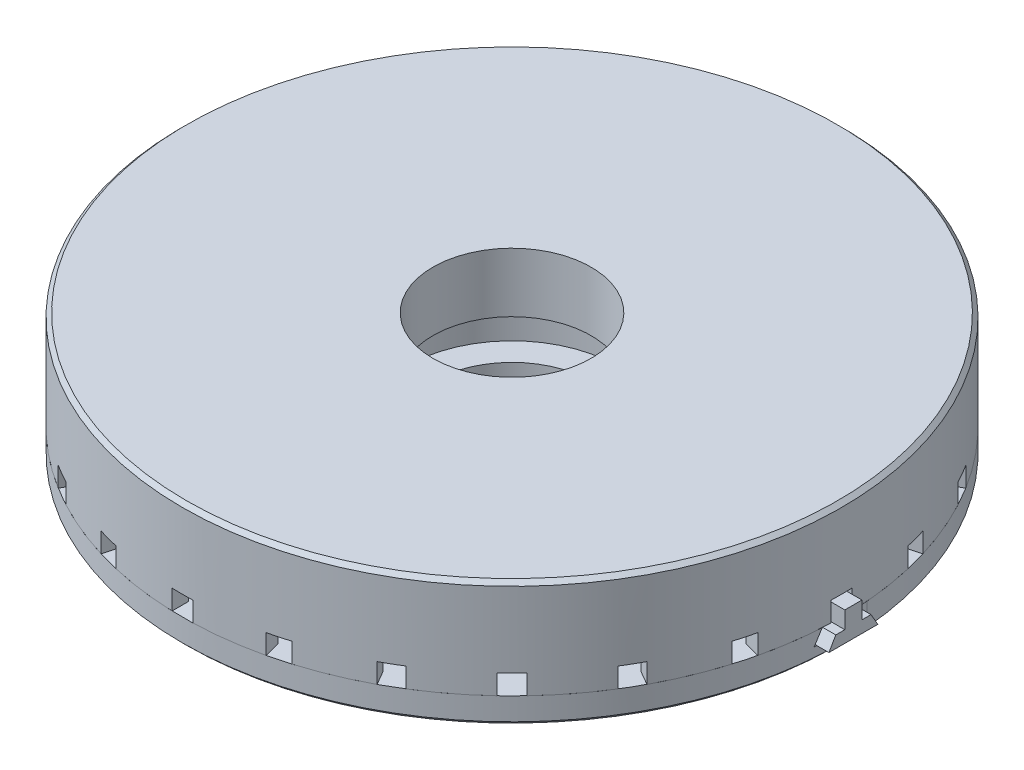
SolidWorks part; units mm, degrees
other "Base_fija"
other "Seguro"
other "Plato_gira"
ref_plane "Front Plane" through (0, 0, 0) normal (0, 0, 1) x (1, 0, 0)
ref_plane "Top Plane" through (0, 0, 0) normal (0, 1, 0) x (1, 0, 0)
ref_plane "Right Plane" through (0, 0, 0) normal (1, 0, 0) x (0, 0, -1)
ref_plane "Plano_Top Plane_+16" through (0, 16, 0) normal (0, 1, 0) x (1, 0, 0)
sketch "Croquis_plato" plane through (0, 16, 0) normal (0, 1, 0) x (1, 0, 0)
  circle A0 centre (0, 0) radius 50
  dimension "D1" = 100
extrude "Plato" add sketch "Croquis_plato" along normal blind 3
sketch "Croquis_falda" plane through (0, 16, 0) normal (0, 1, 0) x (1, 0, 0)
  circle A0 centre (0, 0) radius 50
  circle A1 centre (0, 0) radius 47.5
  dimension "D1" = 95
extrude "Falda" add sketch "Croquis_falda" against normal blind 12
sketch "Croquis_dedos" plane through (0, 0, 0) normal (0, 0, 1) x (1, 0, 0)
  line L0 (0, 0) -> (0, 20) construction
  line L1 (23.3, 16.5) -> (24.5, 16.5)
  line L2 (24.5, 16.5) -> (24.5, 4.5)
  line L3 (24.5, 4.5) -> (23, 4.5)
  line L4 (23, 4.5) -> (22.3, 5.2)
  line L5 (22.3, 5.2) -> (22.3, 5.5)
  line L6 (22.3, 5.5) -> (23.3, 6.5)
  line L7 (23.3, 6.5) -> (23.3, 16.5)
revolve "Anillo_dedos" add sketch "Croquis_dedos" angle 360 about L0
sketch "Croquis_espiga" plane through (0, 16, 0) normal (0, 1, 0) x (1, 0, 0)
  circle A0 centre (0, 0) radius 15.75
  circle A1 centre (0, 0) radius 12
  dimension "D1" = 31.5
extrude "Espiga_centrado" add sketch "Croquis_espiga" against normal blind 6
sketch "Croquis_paso_cables" plane through (0, 0, 0) normal (0, 1, 0) x (1, 0, 0)
  circle A0 centre (0, 0) radius 12
  dimension "D1" = 24
extrude "Paso_cables" cut sketch "Croquis_paso_cables" along normal through all and the other way through all
ref_plane "Plano_Top Plane_+4" through (0, 4, 0) normal (0, 1, 0) x (1, 0, 0)
sketch "Croquis_separar_dedos" plane through (0, 4, 0) normal (0, 1, 0) x (1, 0, 0)
  line L0 (21.4214, 4.5533) -> (24.4537, 5.1978)
  line L1 (18.3669, 11.9276) -> (20.9668, 13.616)
  line L2 (11.9276, 18.3669) -> (13.616, 20.9668)
  line L3 (4.5533, 21.4214) -> (5.1978, 24.4537)
  line L4 (-4.5533, 21.4214) -> (-5.1978, 24.4537)
  line L5 (-11.9276, 18.3669) -> (-13.616, 20.9668)
  line L6 (-18.3669, 11.9276) -> (-20.9668, 13.616)
  line L7 (-21.4214, 4.5533) -> (-24.4537, 5.1978)
  line L8 (-21.4214, -4.5533) -> (-24.4537, -5.1978)
  line L9 (-18.3669, -11.9276) -> (-20.9668, -13.616)
  line L10 (-11.9276, -18.3669) -> (-13.616, -20.9668)
  line L11 (-4.5533, -21.4214) -> (-5.1978, -24.4537)
  line L12 (4.5533, -21.4214) -> (5.1978, -24.4537)
  line L13 (11.9276, -18.3669) -> (13.616, -20.9668)
  line L14 (18.3669, -11.9276) -> (20.9668, -13.616)
  line L15 (21.4214, -4.5533) -> (24.4537, -5.1978)
  arc A0 (24.4537, 5.1978) -> (20.9668, 13.616) centre (0, 0) ccw
  arc A1 (21.4214, 4.5533) -> (18.3669, 11.9276) centre (0, 0) ccw
  arc A2 (13.616, 20.9668) -> (5.1978, 24.4537) centre (0, 0) ccw
  arc A3 (11.9276, 18.3669) -> (4.5533, 21.4214) centre (0, 0) ccw
  arc A4 (-5.1978, 24.4537) -> (-13.616, 20.9668) centre (0, 0) ccw
  arc A5 (-4.5533, 21.4214) -> (-11.9276, 18.3669) centre (0, 0) ccw
  arc A6 (-20.9668, 13.616) -> (-24.4537, 5.1978) centre (0, 0) ccw
  arc A7 (-18.3669, 11.9276) -> (-21.4214, 4.5533) centre (0, 0) ccw
  arc A8 (-24.4537, -5.1978) -> (-20.9668, -13.616) centre (0, 0) ccw
  arc A9 (-21.4214, -4.5533) -> (-18.3669, -11.9276) centre (0, 0) ccw
  arc A10 (-13.616, -20.9668) -> (-5.1978, -24.4537) centre (0, 0) ccw
  arc A11 (-11.9276, -18.3669) -> (-4.5533, -21.4214) centre (0, 0) ccw
  arc A12 (5.1978, -24.4537) -> (13.616, -20.9668) centre (0, 0) ccw
  arc A13 (4.5533, -21.4214) -> (11.9276, -18.3669) centre (0, 0) ccw
  arc A14 (20.9668, -13.616) -> (24.4537, -5.1978) centre (0, 0) ccw
  arc A15 (18.3669, -11.9276) -> (21.4214, -4.5533) centre (0, 0) ccw
extrude "Separar_dedos" cut sketch "Croquis_separar_dedos" along normal blind 12
sketch "Croquis_muescas" plane through (0, 4, 0) normal (0, 1, 0) x (1, 0, 0)
  line L0 (46.5, -1.6) -> (51, -1.6)
  line L1 (51, -1.6) -> (51, 1.6)
  line L2 (51, 1.6) -> (46.5, 1.6)
  line L3 (46.5, 1.6) -> (46.5, -1.6)
  line L4 (45.3297, 10.4896) -> (49.6763, 11.6543)
  line L5 (49.6763, 11.6543) -> (48.8481, 14.7453)
  line L6 (48.8481, 14.7453) -> (44.5014, 13.5806)
  line L7 (44.5014, 13.5806) -> (45.3297, 10.4896)
  line L8 (41.0702, 21.8644) -> (44.9673, 24.1144)
  line L9 (44.9673, 24.1144) -> (43.3673, 26.8856)
  line L10 (43.3673, 26.8856) -> (39.4702, 24.6356)
  line L11 (39.4702, 24.6356) -> (41.0702, 21.8644)
  line L12 (34.0118, 31.7491) -> (37.1938, 34.9311)
  line L13 (37.1938, 34.9311) -> (34.9311, 37.1938)
  line L14 (34.9311, 37.1938) -> (31.7491, 34.0118)
  line L15 (31.7491, 34.0118) -> (34.0118, 31.7491)
  line L16 (24.6356, 39.4702) -> (26.8856, 43.3673)
  line L17 (26.8856, 43.3673) -> (24.1144, 44.9673)
  line L18 (24.1144, 44.9673) -> (21.8644, 41.0702)
  line L19 (21.8644, 41.0702) -> (24.6356, 39.4702)
  line L20 (13.5806, 44.5014) -> (14.7453, 48.8481)
  line L21 (14.7453, 48.8481) -> (11.6543, 49.6763)
  line L22 (11.6543, 49.6763) -> (10.4896, 45.3297)
  line L23 (10.4896, 45.3297) -> (13.5806, 44.5014)
  line L24 (1.6, 46.5) -> (1.6, 51)
  line L25 (1.6, 51) -> (-1.6, 51)
  line L26 (-1.6, 51) -> (-1.6, 46.5)
  line L27 (-1.6, 46.5) -> (1.6, 46.5)
  line L28 (-10.4896, 45.3297) -> (-11.6543, 49.6763)
  line L29 (-11.6543, 49.6763) -> (-14.7453, 48.8481)
  line L30 (-14.7453, 48.8481) -> (-13.5806, 44.5014)
  line L31 (-13.5806, 44.5014) -> (-10.4896, 45.3297)
  line L32 (-21.8644, 41.0702) -> (-24.1144, 44.9673)
  line L33 (-24.1144, 44.9673) -> (-26.8856, 43.3673)
  line L34 (-26.8856, 43.3673) -> (-24.6356, 39.4702)
  line L35 (-24.6356, 39.4702) -> (-21.8644, 41.0702)
  line L36 (-31.7491, 34.0118) -> (-34.9311, 37.1938)
  line L37 (-34.9311, 37.1938) -> (-37.1938, 34.9311)
  line L38 (-37.1938, 34.9311) -> (-34.0118, 31.7491)
  line L39 (-34.0118, 31.7491) -> (-31.7491, 34.0118)
  line L40 (-39.4702, 24.6356) -> (-43.3673, 26.8856)
  line L41 (-43.3673, 26.8856) -> (-44.9673, 24.1144)
  line L42 (-44.9673, 24.1144) -> (-41.0702, 21.8644)
  line L43 (-41.0702, 21.8644) -> (-39.4702, 24.6356)
  line L44 (-44.5014, 13.5806) -> (-48.8481, 14.7453)
  line L45 (-48.8481, 14.7453) -> (-49.6763, 11.6543)
  line L46 (-49.6763, 11.6543) -> (-45.3297, 10.4896)
  line L47 (-45.3297, 10.4896) -> (-44.5014, 13.5806)
  line L48 (-46.5, 1.6) -> (-51, 1.6)
  line L49 (-51, 1.6) -> (-51, -1.6)
  line L50 (-51, -1.6) -> (-46.5, -1.6)
  line L51 (-46.5, -1.6) -> (-46.5, 1.6)
  line L52 (-45.3297, -10.4896) -> (-49.6763, -11.6543)
  line L53 (-49.6763, -11.6543) -> (-48.8481, -14.7453)
  line L54 (-48.8481, -14.7453) -> (-44.5014, -13.5806)
  line L55 (-44.5014, -13.5806) -> (-45.3297, -10.4896)
  line L56 (-41.0702, -21.8644) -> (-44.9673, -24.1144)
  line L57 (-44.9673, -24.1144) -> (-43.3673, -26.8856)
  line L58 (-43.3673, -26.8856) -> (-39.4702, -24.6356)
  line L59 (-39.4702, -24.6356) -> (-41.0702, -21.8644)
  line L60 (-34.0118, -31.7491) -> (-37.1938, -34.9311)
  line L61 (-37.1938, -34.9311) -> (-34.9311, -37.1938)
  line L62 (-34.9311, -37.1938) -> (-31.7491, -34.0118)
  line L63 (-31.7491, -34.0118) -> (-34.0118, -31.7491)
  line L64 (-24.6356, -39.4702) -> (-26.8856, -43.3673)
  line L65 (-26.8856, -43.3673) -> (-24.1144, -44.9673)
  line L66 (-24.1144, -44.9673) -> (-21.8644, -41.0702)
  line L67 (-21.8644, -41.0702) -> (-24.6356, -39.4702)
  line L68 (-13.5806, -44.5014) -> (-14.7453, -48.8481)
  line L69 (-14.7453, -48.8481) -> (-11.6543, -49.6763)
  line L70 (-11.6543, -49.6763) -> (-10.4896, -45.3297)
  line L71 (-10.4896, -45.3297) -> (-13.5806, -44.5014)
  line L72 (-1.6, -46.5) -> (-1.6, -51)
  line L73 (-1.6, -51) -> (1.6, -51)
  line L74 (1.6, -51) -> (1.6, -46.5)
  line L75 (1.6, -46.5) -> (-1.6, -46.5)
  line L76 (10.4896, -45.3297) -> (11.6543, -49.6763)
  line L77 (11.6543, -49.6763) -> (14.7453, -48.8481)
  line L78 (14.7453, -48.8481) -> (13.5806, -44.5014)
  line L79 (13.5806, -44.5014) -> (10.4896, -45.3297)
  line L80 (21.8644, -41.0702) -> (24.1144, -44.9673)
  line L81 (24.1144, -44.9673) -> (26.8856, -43.3673)
  line L82 (26.8856, -43.3673) -> (24.6356, -39.4702)
  line L83 (24.6356, -39.4702) -> (21.8644, -41.0702)
  line L84 (31.7491, -34.0118) -> (34.9311, -37.1938)
  line L85 (34.9311, -37.1938) -> (37.1938, -34.9311)
  line L86 (37.1938, -34.9311) -> (34.0118, -31.7491)
  line L87 (34.0118, -31.7491) -> (31.7491, -34.0118)
  line L88 (39.4702, -24.6356) -> (43.3673, -26.8856)
  line L89 (43.3673, -26.8856) -> (44.9673, -24.1144)
  line L90 (44.9673, -24.1144) -> (41.0702, -21.8644)
  line L91 (41.0702, -21.8644) -> (39.4702, -24.6356)
  line L92 (44.5014, -13.5806) -> (48.8481, -14.7453)
  line L93 (48.8481, -14.7453) -> (49.6763, -11.6543)
  line L94 (49.6763, -11.6543) -> (45.3297, -10.4896)
  line L95 (45.3297, -10.4896) -> (44.5014, -13.5806)
extrude "Muescas_seguro" cut sketch "Croquis_muescas" along normal blind 3
chamfer "Chaflan_cara_superior" distance 0.6 angle 45 1 edges at (0, 19, 50) tangent propagation no
sketch "Croquis_base" plane through (0, 0, 0) normal (0, 1, 0) x (1, 0, 0)
  circle A0 centre (0, 0) radius 50
  dimension "D1" = 100
extrude "Base" add sketch "Croquis_base" along normal blind 4 separate body
sketch "Croquis_nucleo" plane through (0, 0, 0) normal (0, 0, 1) x (1, 0, 0)
  line L0 (0, 0) -> (0, 20) construction
  line L1 (16, 3.5) -> (21.5, 3.5)
  line L2 (21.5, 3.5) -> (21.5, 5)
  line L3 (21.5, 5) -> (23, 6.5)
  line L4 (23, 6.5) -> (23, 14.6)
  line L5 (23, 14.6) -> (22, 15.6)
  line L6 (22, 15.6) -> (16, 15.6)
  line L7 (16, 15.6) -> (16, 3.5)
revolve "Nucleo" add sketch "Croquis_nucleo" angle 360 about L0
combine bodies "Sumar_nucleo_a_base" operation type add bodies to combine 108 109
ref_plane "Plano_Top Plane_+15_6" through (0, 15.6, 0) normal (0, 1, 0) x (1, 0, 0)
sketch "Croquis_ranuras_clic" plane through (0, 15.6, 0) normal (0, 1, 0) x (1, 0, 0)
  line L0 (22.5, 0) -> (23.2, -0.7)
  line L1 (23.2, -0.7) -> (23.2, 0.7)
  line L2 (23.2, 0.7) -> (22.5, 0)
  line L3 (21.7333, 5.8234) -> (22.5907, 5.3285)
  line L4 (22.5907, 5.3285) -> (22.2283, 6.6807)
  line L5 (22.2283, 6.6807) -> (21.7333, 5.8234)
  line L6 (19.4856, 11.25) -> (20.4418, 10.9938)
  line L7 (20.4418, 10.9938) -> (19.7418, 12.2062)
  line L8 (19.7418, 12.2062) -> (19.4856, 11.25)
  line L9 (15.9099, 15.9099) -> (16.8999, 15.9099)
  line L10 (16.8999, 15.9099) -> (15.9099, 16.8999)
  line L11 (15.9099, 16.8999) -> (15.9099, 15.9099)
  line L12 (11.25, 19.4856) -> (12.2062, 19.7418)
  line L13 (12.2062, 19.7418) -> (10.9938, 20.4418)
  line L14 (10.9938, 20.4418) -> (11.25, 19.4856)
  line L15 (5.8234, 21.7333) -> (6.6807, 22.2283)
  line L16 (6.6807, 22.2283) -> (5.3285, 22.5907)
  line L17 (5.3285, 22.5907) -> (5.8234, 21.7333)
  line L18 (0, 22.5) -> (0.7, 23.2)
  line L19 (0.7, 23.2) -> (-0.7, 23.2)
  line L20 (-0.7, 23.2) -> (0, 22.5)
  line L21 (-5.8234, 21.7333) -> (-5.3285, 22.5907)
  line L22 (-5.3285, 22.5907) -> (-6.6807, 22.2283)
  line L23 (-6.6807, 22.2283) -> (-5.8234, 21.7333)
  line L24 (-11.25, 19.4856) -> (-10.9938, 20.4418)
  line L25 (-10.9938, 20.4418) -> (-12.2062, 19.7418)
  line L26 (-12.2062, 19.7418) -> (-11.25, 19.4856)
  line L27 (-15.9099, 15.9099) -> (-15.9099, 16.8999)
  line L28 (-15.9099, 16.8999) -> (-16.8999, 15.9099)
  line L29 (-16.8999, 15.9099) -> (-15.9099, 15.9099)
  line L30 (-19.4856, 11.25) -> (-19.7418, 12.2062)
  line L31 (-19.7418, 12.2062) -> (-20.4418, 10.9938)
  line L32 (-20.4418, 10.9938) -> (-19.4856, 11.25)
  line L33 (-21.7333, 5.8234) -> (-22.2283, 6.6807)
  line L34 (-22.2283, 6.6807) -> (-22.5907, 5.3285)
  line L35 (-22.5907, 5.3285) -> (-21.7333, 5.8234)
  line L36 (-22.5, 0) -> (-23.2, 0.7)
  line L37 (-23.2, 0.7) -> (-23.2, -0.7)
  line L38 (-23.2, -0.7) -> (-22.5, 0)
  line L39 (-21.7333, -5.8234) -> (-22.5907, -5.3285)
  line L40 (-22.5907, -5.3285) -> (-22.2283, -6.6807)
  line L41 (-22.2283, -6.6807) -> (-21.7333, -5.8234)
  line L42 (-19.4856, -11.25) -> (-20.4418, -10.9938)
  line L43 (-20.4418, -10.9938) -> (-19.7418, -12.2062)
  line L44 (-19.7418, -12.2062) -> (-19.4856, -11.25)
  line L45 (-15.9099, -15.9099) -> (-16.8999, -15.9099)
  line L46 (-16.8999, -15.9099) -> (-15.9099, -16.8999)
  line L47 (-15.9099, -16.8999) -> (-15.9099, -15.9099)
  line L48 (-11.25, -19.4856) -> (-12.2062, -19.7418)
  line L49 (-12.2062, -19.7418) -> (-10.9938, -20.4418)
  line L50 (-10.9938, -20.4418) -> (-11.25, -19.4856)
  line L51 (-5.8234, -21.7333) -> (-6.6807, -22.2283)
  line L52 (-6.6807, -22.2283) -> (-5.3285, -22.5907)
  line L53 (-5.3285, -22.5907) -> (-5.8234, -21.7333)
  line L54 (0, -22.5) -> (-0.7, -23.2)
  line L55 (-0.7, -23.2) -> (0.7, -23.2)
  line L56 (0.7, -23.2) -> (0, -22.5)
  line L57 (5.8234, -21.7333) -> (5.3285, -22.5907)
  line L58 (5.3285, -22.5907) -> (6.6807, -22.2283)
  line L59 (6.6807, -22.2283) -> (5.8234, -21.7333)
  line L60 (11.25, -19.4856) -> (10.9938, -20.4418)
  line L61 (10.9938, -20.4418) -> (12.2062, -19.7418)
  line L62 (12.2062, -19.7418) -> (11.25, -19.4856)
  line L63 (15.9099, -15.9099) -> (15.9099, -16.8999)
  line L64 (15.9099, -16.8999) -> (16.8999, -15.9099)
  line L65 (16.8999, -15.9099) -> (15.9099, -15.9099)
  line L66 (19.4856, -11.25) -> (19.7418, -12.2062)
  line L67 (19.7418, -12.2062) -> (20.4418, -10.9938)
  line L68 (20.4418, -10.9938) -> (19.4856, -11.25)
  line L69 (21.7333, -5.8234) -> (22.2283, -6.6807)
  line L70 (22.2283, -6.6807) -> (22.5907, -5.3285)
  line L71 (22.5907, -5.3285) -> (21.7333, -5.8234)
extrude "Ranuras_clic" cut sketch "Croquis_ranuras_clic" against normal blind 9.1
sketch "Croquis_paso_cables_base" plane through (0, 0, 0) normal (0, 1, 0) x (1, 0, 0)
  circle A0 centre (0, 0) radius 12
  dimension "D1" = 24
extrude "Paso_cables_base" cut sketch "Croquis_paso_cables_base" along normal through all and the other way through all
ref_plane "Plano_Right Plane_+37_3" through (37.3, 0, 0) normal (1, 0, 0) x (0, 0, -1)
sketch "Croquis_canal_seguro" plane through (37.3, 0, 0) normal (1, 0, 0) x (0, 0, -1)
  line L0 (-4, 2) -> (4, 2)
  line L1 (4, 2) -> (2.8453, 4)
  line L2 (2.8453, 4) -> (-2.8453, 4)
  line L3 (-2.8453, 4) -> (-4, 2)
extrude "Canal_seguro" cut sketch "Croquis_canal_seguro" along normal through all
chamfer "Chaflan_base" distance 0.6 angle 45 1 edges at (0, 0, 50) tangent propagation no
ref_plane "Plano_Top Plane_+6_8" through (0, 6.8, 0) normal (0, 1, 0) x (1, 0, 0)
sketch "Croquis_costillas_clic" plane through (0, 6.8, 0) normal (0, 1, 0) x (1, 0, 0)
  line L0 (0, 22.7) -> (0.7, 23.4)
  line L1 (0.7, 23.4) -> (-0.7, 23.4)
  line L2 (-0.7, 23.4) -> (0, 22.7)
  line L3 (0, -22.7) -> (-0.7, -23.4)
  line L4 (-0.7, -23.4) -> (0.7, -23.4)
  line L5 (0.7, -23.4) -> (0, -22.7)
extrude "Costillas_clic" add sketch "Croquis_costillas_clic" along normal blind 2.5 separate body
combine bodies "Sumar_costillas_a_plato" operation type add bodies to combine 107 114 115
ref_plane "Plano_Right Plane_+37_5" through (37.5, 0, 0) normal (1, 0, 0) x (0, 0, -1)
sketch "Croquis_seguro" plane through (37.5, 0, 0) normal (1, 0, 0) x (0, 0, -1)
  line L0 (-3.7113, 2.1) -> (3.7113, 2.1)
  line L1 (3.7113, 2.1) -> (2.6721, 3.9)
  line L2 (2.6721, 3.9) -> (-2.6721, 3.9)
  line L3 (-2.6721, 3.9) -> (-3.7113, 2.1)
extrude "Pasador_seguro" add sketch "Croquis_seguro" along normal blind 14.3 separate body
ref_plane "Plano_Top Plane_+3_9" through (0, 3.9, 0) normal (0, 1, 0) x (1, 0, 0)
sketch "Croquis_diente" plane through (0, 3.9, 0) normal (0, 1, 0) x (1, 0, 0)
  line L0 (51.8, 2.6721) -> (51.8, -2.6721) construction
  line L1 (47, -1.3) -> (51.8, -1.3)
  line L2 (47, -1.3) -> (47, 1.3)
  line L3 (47, 1.3) -> (51.8, 1.3)
  line L4 (51.8, -1.3) -> (51.8, 1.3)
  line L5 (47, -1.3) -> (51.8, 1.3) construction
  line L6 (47, 1.3) -> (51.8, -1.3) construction
  circle A0 centre (0, 0) radius 49.4 construction
  point P0 (49.4, 0)
  dimension "D1" = 4.8
  dimension "D2" = 2.6
extrude "Diente_seguro" add sketch "Croquis_diente" along normal blind 2.6 separate body
combine bodies "Sumar_diente_a_seguro" operation type add bodies to combine 117 118
